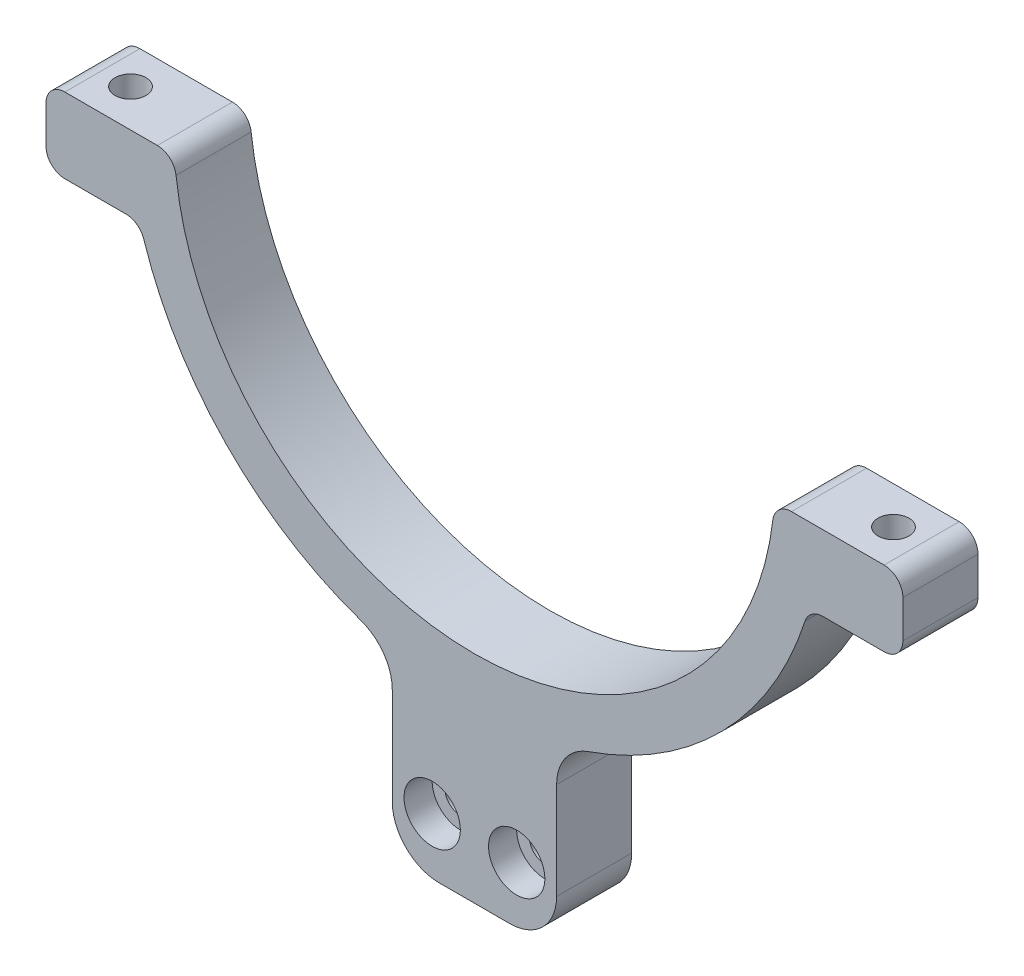
SolidWorks part; units mm, degrees
ref_plane "Front Plane" through (0, 0, 0) normal (0, 0, 1) x (1, 0, 0)
ref_plane "Top Plane" through (0, 0, 0) normal (0, 1, 0) x (1, 0, 0)
ref_plane "Right Plane" through (0, 0, 0) normal (1, 0, 0) x (0, 0, -1)
sketch "Sketch2" plane through (0, 0, 0) normal (0, 0, 1) x (1, 0, 0)
  circle A0 centre (0, 0) radius 31.7 construction
  dimension "D1" = 63.4
sketch "Sketch3" plane through (0, 0, 0) normal (0, 0, 1) x (1, 0, 0)
  line L0 (-31.9374, -2) -> (-45.623, -2)
  line L1 (31.9374, -2) -> (45.623, -2)
  line L7 (-11, -35.327) -> (-11, -80.1)
  line L8 (-11, -80.1) -> (11, -80.1)
  line L9 (11, -80.1) -> (11, -35.327)
  line L11 (35.623, -10) -> (45.623, -10)
  line L12 (45.623, -10) -> (45.623, -2)
  line L13 (-35.623, -10) -> (-45.623, -10)
  line L14 (-45.623, -10) -> (-45.623, -2)
  line L15 (40.623, -10) -> (40.623, -2) construction
  line L16 (37.623, -6) -> (43.623, -6) construction
  circle A1 centre (0, -69.1) radius 4 construction
  arc A2 (31.9374, -2) -> (-31.9374, -2) centre (0, 0) cw
  circle A3 centre (0, 0) radius 31.7 construction
  circle A7 centre (0, -69.1) radius 8.05
  arc A8 (11, -35.327) -> (35.623, -10) centre (0, 0) ccw
  arc A9 (-11, -35.327) -> (-35.623, -10) centre (0, 0) cw
  point P9 (0, -80.1)
  point P24 (40.623, -6)
  dimension "D1" = 0.3
  dimension "D3" = 37.4
  dimension "D4" = 8
  dimension "D5" = 16.1
  dimension "D7" = 5
  dimension "D2" = 48.4
  dimension "D6" = 22
  dimension "D8" = 8
  dimension "D9" = 6
  dimension "D10" = 2
  dimension "D11" = 2
  dimension "D12" = 2
extrude "Boss-Extrude1" add sketch "Sketch3" along normal blind 8
sketch "Sketch4" plane through (0, 0, 0) normal (0, 0, 1) x (1, 0, 0)
  circle A0 centre (0, -69.1) radius 8.05 construction
  circle A1 centre (0, -69.1) radius 8.05
  circle A2 centre (0, -69.1) radius 4.3
  dimension "D1" = 8.6
extrude "Boss-Extrude2" add sketch "Sketch4" along normal offset from surface (3 mm away) 5 up to face at (0, -26.2592, 8)
chamfer "Chamfer1" distance 3 angle 45 1 edges at (0, -80.1, 0)
fillet "Fillet1" radius 11 2 edges at (-11, -80.1, 5.5) (11, -80.1, 5.5)
sketch "Sketch5" plane through (0, -10, 0) normal (0, -1, 0) x (1, 0, 0)
  line L0 (37.623, 0) -> (43.623, 0) construction
  line L1 (37.623, 0) -> (43.623, 0) construction
  line L2 (40.623, 0) -> (40.623, 8) construction
  line L3 (45.623, 8) -> (31.9374, 8) construction
  line L4 (0, 0) -> (0, 8) construction
  line L5 (31.7, 0) -> (-31.7, 0) construction
  line L6 (31.9374, 8) -> (-31.9374, 8) construction
  circle A0 centre (40.623, 4) radius 1.65
  dimension "D1" = 3.3
extrude "Cut-Extrude1" cut sketch "Sketch5" against normal through all
sketch "Sketch6" plane through (0, -10, 0) normal (0, -1, 0) x (1, 0, 0)
  circle A0 centre (40.623, 4) radius 3
  dimension "D1" = 6
extrude "Cut-Extrude2" cut sketch "Sketch6" against normal blind 3
mirror "Mirror1" about plane through (0, 0, 0) normal (1, 0, 0) of "Cut-Extrude2", "Cut-Extrude1"
sketch "Sketch7" plane through (0, 0, 8) normal (0, 0, 1) x (1, 0, 0)
  line L0 (-11, -35.327) -> (-11, -69.1) construction
  line L1 (-11, -55) -> (11, -55)
  line L2 (-11, -55) -> (-11, -80.1)
  line L3 (-11, -80.1) -> (11, -80.1)
  line L4 (11, -55) -> (11, -80.1)
  line L5 (-11, -55) -> (11, -80.1) construction
  line L6 (-11, -80.1) -> (11, -55) construction
  line L7 (11, -69.1) -> (11, -35.327) construction
  point P4 (0, -67.55)
  dimension "D1" = 55
extrude "Cut-Extrude3" cut sketch "Sketch7" against normal through all
fillet "Fillet2" radius 2 8 edges at (-35.623, -10, 4) (-45.623, -2, 4) (-31.9374, -2, 4) (31.9374, -2, 4) (45.623, -2, 4) (45.623, -10, 4) (35.623, -10, 4) (-45.623, -10, 4)
sketch "Sketch8" plane through (0, 0, 8) normal (0, 0, 1) x (1, 0, 0)
  line L0 (-4.5, -49) -> (4.5, -49) construction
  circle A2 centre (4.5, -49) radius 1.65
  circle A3 centre (-4.5, -49) radius 1.65
  point P3 (0, -49)
  dimension "D1" = 3.3
  dimension "D2" = 9
  dimension "D3" = 49
extrude "Cut-Extrude4" cut sketch "Sketch8" against normal through all
sketch "Sketch9" plane through (0, 0, 8) normal (0, 0, 1) x (1, 0, 0)
  line L0 (-8.75, -55) -> (-8.75, -35.9505)
  line L1 (11, -55) -> (-11, -55) construction
  line L2 (8.75, -55) -> (8.75, -35.9505)
  line L3 (-8.75, -45.4752) -> (8.75, -45.4752) construction
  line L4 (-11, -35.327) -> (-11, -55)
  line L5 (-11, -55) -> (-8.75, -55)
  line L6 (8.75, -55) -> (11, -55)
  line L7 (11, -55) -> (11, -35.327)
  arc A0 (-8.75, -35.9505) -> (-11, -35.327) centre (0, 0) cw
  arc A1 (8.75, -35.9505) -> (11, -35.327) centre (0, 0) ccw
  arc A2 (11, -35.327) -> (35.205, -11.3846) centre (0, 0) ccw construction
  point P10 (0, -45.4752)
  dimension "D1" = 17.5
extrude "Cut-Extrude5" cut sketch "Sketch9" against normal through all
fillet "Fillet3" radius 5 4 edges at (-8.75, -55, 4) (8.75, -55, 4) (8.75, -35.9505, 4) (-8.75, -35.9505, 4)
sketch "Sketch10" plane through (0, 0, 8) normal (0, 0, 1) x (1, 0, 0)
  circle A0 centre (4.5, -49) radius 3
  circle A1 centre (-4.5, -49) radius 3
  dimension "D1" = 6
extrude "Cut-Extrude6" cut sketch "Sketch10" against normal blind 3
